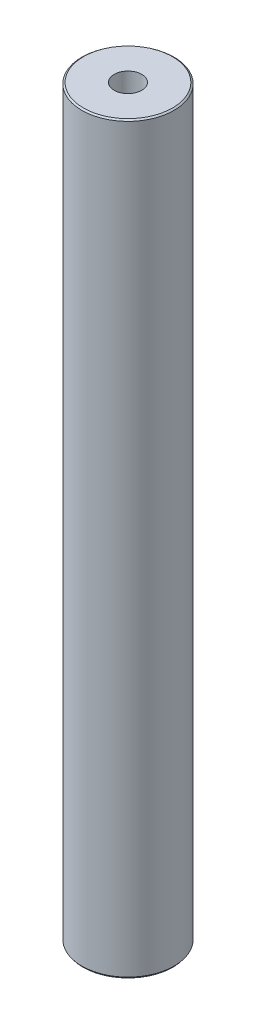
SolidWorks part; units mm, degrees
ref_plane "Front Plane" through (0, 0, 0) normal (0, 0, 1) x (1, 0, 0)
ref_plane "Top Plane" through (0, 0, 0) normal (0, 1, 0) x (1, 0, 0)
ref_plane "Right Plane" through (0, 0, 0) normal (1, 0, 0) x (0, 0, -1)
sketch "Sketch1" plane through (0, 0, 0) normal (0, 1, 0) x (1, 0, 0)
  circle A0 centre (0, 0) radius 12.5
  dimension "SHAFT_OD" = 25
extrude "Boss-Extrude1" add sketch "Sketch1" along normal blind 201.6408
sketch "Sketch2" plane through (0, 0, 0) normal (0, 1, 0) x (1, 0, 0)
  circle A0 centre (0, 0) radius 3.7485
  dimension "BORE_D" = 7.497
extrude "Cut-Extrude1" cut sketch "Sketch2" along normal through all
chamfer "Chamfer1" distance 0.3285 angle 53.168 2 edges at (0, 201.6408, 12.5) (0, 0, 12.5) first distance on face at (0, 201.6408, 12.5) first distance on face at (0, 0, 3.7485)
